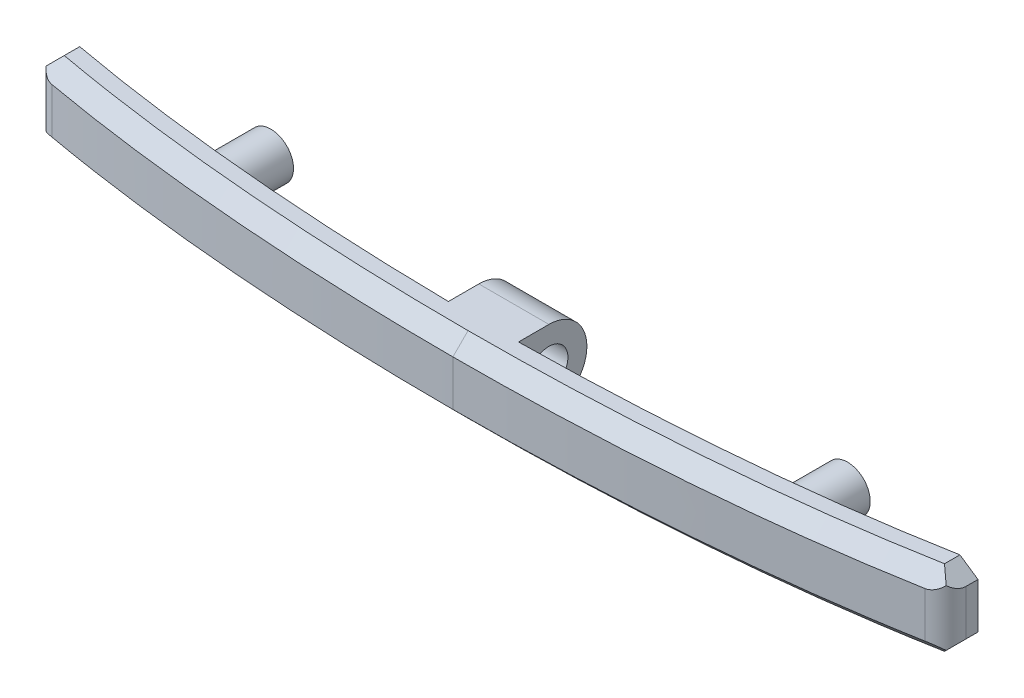
SolidWorks part; units mm, degrees
ref_plane "Alzado" through (0, 0, 0) normal (0, 0, 1) x (1, 0, 0)
ref_plane "Planta" through (0, 0, 0) normal (0, 1, 0) x (1, 0, 0)
ref_plane "Vista lateral" through (0, 0, 0) normal (1, 0, 0) x (0, 0, -1)
sketch "Guia" plane through (0, 0, 0) normal (1, 0, 0) x (0, 0, -1)
  line L0 (0, 20.2) -> (0, 0)
  line L1 (-100, 0) -> (0, 0)
  line L2 (0, 20.2) -> (28.4023, 28.8834)
  line L3 (0, 20.2) -> (-66.0712, 0)
  line L4 (-26, 12.251) -> (-26, 0)
  circle A0 centre (0, 20.2) radius 1.5
  circle A1 centre (28.4023, 28.8834) radius 1.5
  dimension "D1" = 3
  dimension "D2" = 3
  dimension "D3" = 17
  dimension "D4" = 20.2
  dimension "D5" = 29.7
  dimension "D6" = 100
  dimension "D7" = 26
sketch "Croquis5" plane through (0, 0, 0) normal (0, 1, 0) x (1, 0, 0)
  line L1 (0, -26) -> (0, -30)
  line L2 (0, -100) -> (0, 0) construction
  line L3 (60, -20.8) -> (60, -24.8738)
  ellipse E0 centre (0, 0) end of major axis (100, 0) minor radius 26 (0, -26) -> (60, -20.8) ccw
  spline S1 degree 3 poles (0, -30) (3.3065, -30) (16.5326, -29.8312) (35.9976, -28.5653) (52.0571, -26.3332) (58.7663, -25.1098) (60, -24.8738) knots 4.712389 4.712389 4.712389 4.712389 4.810564 5.105088 5.301438 5.346535 5.346535 5.346535 5.346535
  dimension "D1" = 200
  dimension "D3" = 60
extrude "Saliente-Extruir2" add sketch "Croquis5" along normal mid plane 10 separate body
ref_plane "Plano1" through (0, 0, 26) normal (0, 0, 1) x (1, 0, 0)
sketch "Croquis6" plane through (0, 0, 26) normal (0, 0, 1) x (1, 0, 0)
  circle A0 centre (38, 0) radius 3
  dimension "D1" = 6
  dimension "D2" = 38
extrude "Saliente-Extruir3" add sketch "Croquis6" against normal blind 10
sketch "Croquis7" plane through (0, 0, 16) normal (0, 0, -1) x (-1, 0, 0)
  circle A0 centre (-38, 0) radius 1.75
  dimension "D1" = 3.5
extrude "Cortar-Extruir1" cut sketch "Croquis7" against normal blind 10
chamfer "Chaflán1" distance 2 angle 45 4 edges at (60, -5, 22.8369) (60, 5, 22.8369)
fillet "Redondeo2" radius 3 1 edges
ref_plane "Plano2" through (0, 26, 0) normal (0, 1, 0) x (1, 0, 0)
sketch "Croquis17" plane through (0, 0, 0) normal (1, 0, 0) x (0, 0, -1)
  line L0 (-21.961, 5) -> (-21.961, -4.1031) construction
  line L2 (-21.961, -5) -> (-26.961, -5)
  line L3 (-18.1504, -4.6474) -> (-18.1504, -3.2372)
  line L4 (-21.961, 5) -> (-26.961, 5)
  line L5 (-26.961, -5) -> (-26.961, 5)
  line L6 (-18.4254, -3.5355) -> (-26.961, 5) construction
  line L7 (-18.4254, 3.5355) -> (-26.961, -5) construction
  line L8 (-21.961, 0) -> (-16.961, 0) construction
  line L10 (-26, -5) -> (-21.18, -5) construction
  line L11 (-26, 5) -> (-26, -5) construction
  circle A0 centre (-21.961, 0) radius 2.5
  arc A1 (-21.961, 5) -> (-21.961, -5) centre (-21.961, 0) cw
  dimension "D1" = 5
  dimension "D2" = 2.5
  dimension "D3" = 0.961
extrude "Saliente-Extruir8" add sketch "Croquis17" along normal blind 4.62 and the other way blind 4.62 contours A1 L4 L5 L2 A0 region at (0, -4.8586, 24.461)
mirror "Simetría2" about plane through (0, 0, 0) normal (1, 0, 0) of bodies 120
